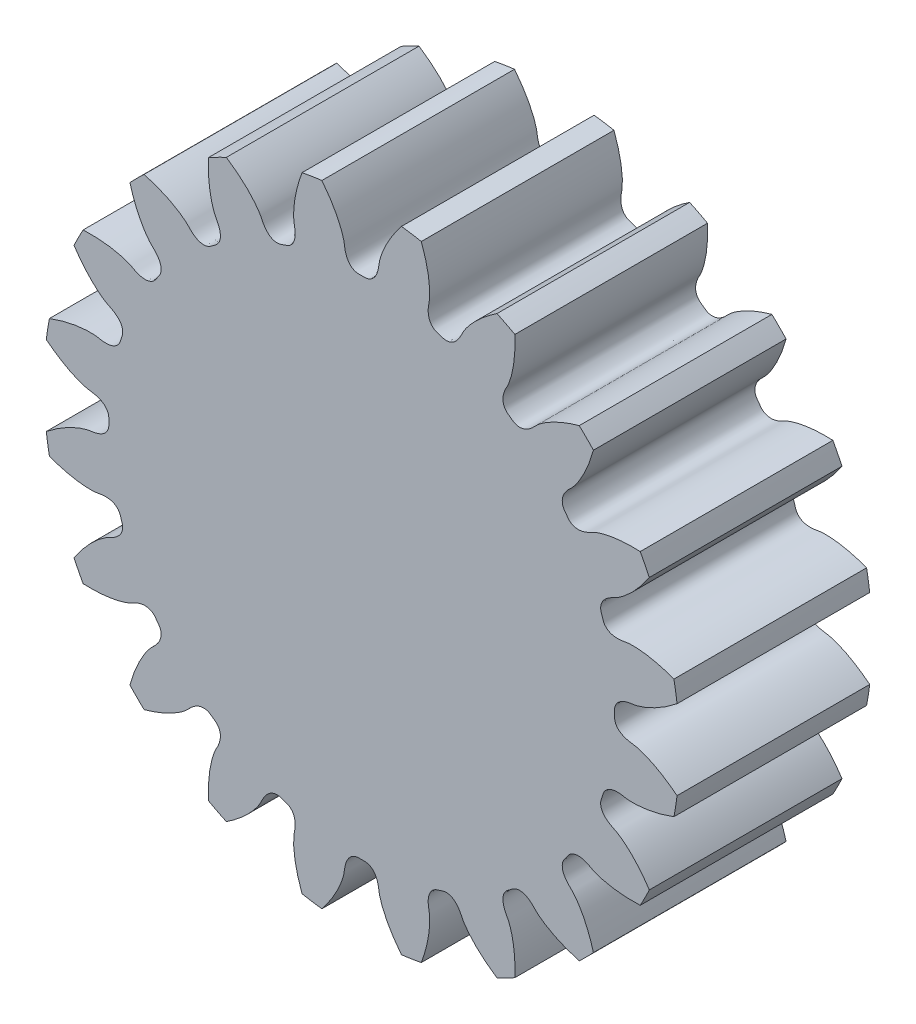
SolidWorks part; units mm, degrees
ref_plane "Front Plane" through (0, 0, 0) normal (0, 0, 1) x (1, 0, 0)
ref_plane "Top Plane" through (0, 0, 0) normal (0, 1, 0) x (1, 0, 0)
ref_plane "Right Plane" through (0, 0, 0) normal (1, 0, 0) x (0, 0, -1)
ref_axis "Axis1" through (0, 0, 55) along (0, 0, -1)
sketch "SketchRevolveSpurAssembly01Pinion" plane through (0, 0, 0) normal (1, 0, 0) x (0, 0, -1)
  line L0 (0, 0) -> (1, 0) construction
  line L1 (-5, 0) -> (-5, 16.5)
  line L2 (-5, 16.5) -> (5, 16.5)
  line L3 (5, 16.5) -> (5, 0)
  line L4 (5, 0) -> (-5, 0)
  dimension "Side1" = 5
  dimension "OutsideRadius" = 16.5
  dimension "Side2" = 5
revolve "SpurAssembly01Pinion" add sketch "SketchRevolveSpurAssembly01Pinion" angle 360 about L0
sketch "SketchToothSpurAssembly01Pinion" plane through (0, 0, 0) normal (0, 0, 1) x (1, 0, 0)
  arc A0 (16.4388, 2.1204) -> (16.4388, -2.1204) centre (0, 0) cw
  spline S0 degree 3 poles (16.4388, -2.1204) (16.3062, -2.0126) (16.1079, -1.8609) (15.8417, -1.6767) (15.6549, -1.5557) (15.4759, -1.4476) (15.3054, -1.3516) (15.1441, -1.2672) (14.9923, -1.1937) (14.8506, -1.1305) (14.7196, -1.0767) (14.5996, -1.0318) (14.491, -0.9949) (14.3942, -0.9653) (14.3096, -0.9423) (14.2375, -0.925) (14.178, -0.9126) (14.0492, -0.8903) (13.9123, -0.8782) (13.7697, -0.8427) (13.6956, -0.8206) (13.6244, -0.795) (13.5557, -0.7654) (13.4893, -0.7311) (13.4248, -0.6913) (13.3623, -0.6446) (13.3021, -0.5892) (13.2452, -0.523) (13.1943, -0.4439) (13.1533, -0.3509) (13.1303, -0.2534) (13.1208, -0.135) (13.1277, 0) (13.1208, 0.135) (13.1303, 0.2534) (13.1533, 0.3509) (13.1943, 0.4439) (13.2452, 0.523) (13.3021, 0.5892) (13.3623, 0.6446) (13.4248, 0.6913) (13.4893, 0.7311) (13.5557, 0.7654) (13.6244, 0.795) (13.6956, 0.8206) (13.7697, 0.8427) (13.9123, 0.8782) (14.0492, 0.8903) (14.178, 0.9126) (14.2375, 0.925) (14.3096, 0.9423) (14.3942, 0.9653) (14.491, 0.9949) (14.5996, 1.0318) (14.7196, 1.0767) (14.8506, 1.1305) (14.9923, 1.1937) (15.1441, 1.2672) (15.3054, 1.3516) (15.4759, 1.4476) (15.6549, 1.5557) (15.8417, 1.6767) (16.1079, 1.8609) (16.3062, 2.0126) (16.4388, 2.1204) knots 0 0 0 0 0.061423 0.08971 0.11638 0.141434 0.164872 0.186693 0.206898 0.225486 0.242459 0.257814 0.271554 0.283677 0.294183 0.303073 0.310347 0.316004 0.350077 0.359568 0.368803 0.377844 0.386769 0.395676 0.404689 0.413963 0.423683 0.434051 0.445256 0.457401 0.47042 0.481067 0.5 0.518933 0.52958 0.542599 0.554744 0.565949 0.576317 0.586037 0.595311 0.604324 0.613231 0.622156 0.631197 0.640432 0.649923 0.683996 0.689653 0.696927 0.705817 0.716323 0.728446 0.742186 0.757541 0.774514 0.793102 0.813307 0.835128 0.858566 0.88362 0.91029 0.938577 1 1 1 1
extrude "ToothExtrudeCutSpurAssembly01Pinion" cut sketch "SketchToothSpurAssembly01Pinion" against normal blind 5 and the other way blind 5
pattern_circular "PatternSpurAssembly01Pinion" count 20 every 18 about axis through (0, 0, 55) along (0, 0, -1) of "ToothExtrudeCutSpurAssembly01Pinion"
sketch "AuxiliarySketchSpurAssembly01Pinion" plane through (0, 0, 0) normal (0, 0, 1) x (1, 0, 0)
  circle A0 centre (0, 0) radius 15 construction
  circle A1 centre (0, 0) radius 14.0954 construction
  circle A2 centre (0, 0) radius 14.1048 construction
  circle A3 centre (0, 0) radius 16.5 construction
  circle A4 centre (0, 0) radius 13.125 construction
  dimension "PitchDiameter" = 30
  dimension "BaseDiameter" = 28.1908
  dimension "FormDiameter" = 28.2095
  dimension "MajorDiameter" = 33
  dimension "MinorDiameter" = 26.25
sketch "Sketch1" plane through (0, 0, 5) normal (0, 0, 1) x (1, 0, 0)
  line L0 (0, 0) -> (0, 1.5) construction
  line L1 (0, 1.5) -> (1.3229, 1.5) construction
  line L2 (0, 1.5) -> (-1.3229, 1.5) construction
  line L3 (-1.3229, 1.5) -> (1.3229, 1.5)
  circle A0 centre (0, 0) radius 2 construction
  arc A1 (-1.3229, 1.5) -> (1.3229, 1.5) centre (0, 0) ccw
  point P6 (0, 0)
